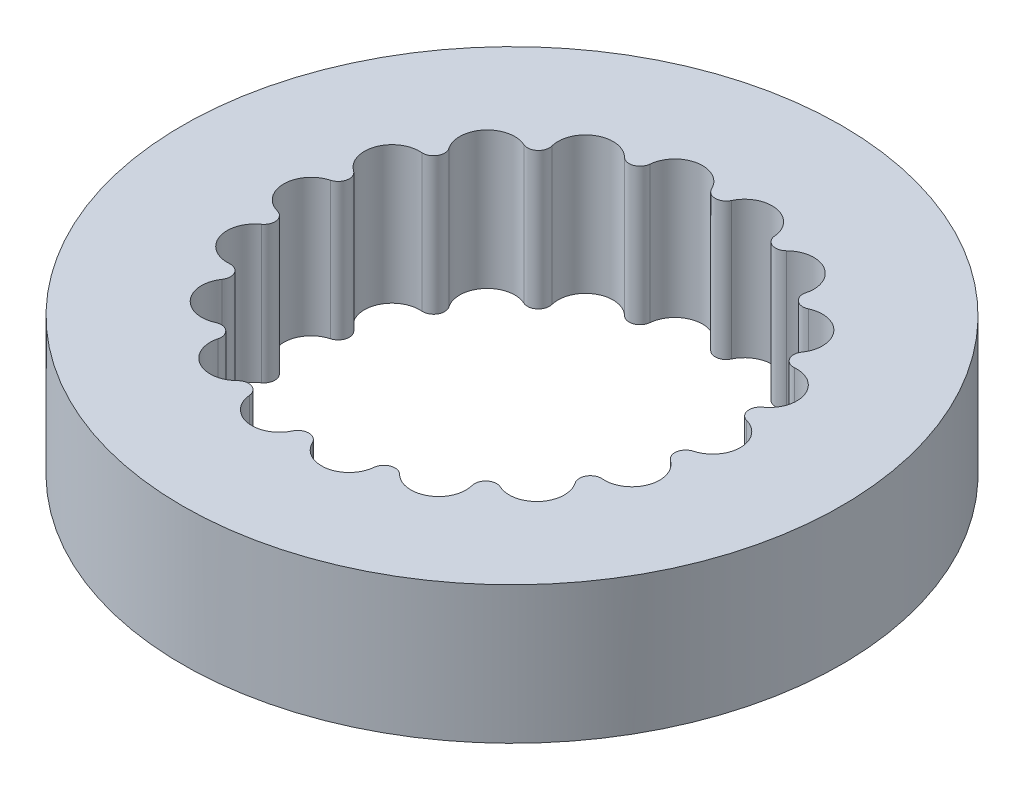
SolidWorks part; units mm, degrees
ref_plane "Front Plane" through (0, 0, 0) normal (0, 0, 1) x (1, 0, 0)
ref_plane "Top Plane" through (0, 0, 0) normal (0, 1, 0) x (1, 0, 0)
ref_plane "Right Plane" through (0, 0, 0) normal (1, 0, 0) x (0, 0, -1)
sketch "Sketch1" plane through (0, 0, 0) normal (0, 1, 0) x (1, 0, 0)
  circle A0 centre (0, 0) radius 39 construction
  circle A1 centre (0, 39) radius 2
  circle A2 centre (13.3388, 36.648) radius 2
  circle A3 centre (25.0687, 29.8757) radius 2
  circle A4 centre (33.775, 19.5) radius 2
  circle A5 centre (38.4075, 6.7723) radius 2
  circle A6 centre (38.4075, -6.7723) radius 2
  circle A7 centre (33.775, -19.5) radius 2
  circle A8 centre (25.0687, -29.8757) radius 2
  circle A9 centre (13.3388, -36.648) radius 2
  circle A10 centre (0, -39) radius 2
  circle A11 centre (-13.3388, -36.648) radius 2
  circle A12 centre (-25.0687, -29.8757) radius 2
  circle A13 centre (-33.775, -19.5) radius 2
  circle A14 centre (-38.4075, -6.7723) radius 2
  circle A15 centre (-38.4075, 6.7723) radius 2
  circle A16 centre (-33.775, 19.5) radius 2
  circle A17 centre (-25.0687, 29.8757) radius 2
  circle A18 centre (-13.3388, 36.648) radius 2
  circle A19 centre (0, 0) radius 45
  circle A20 centre (0, 0) radius 30
  point P42 (0, 0)
  dimension "D1" = 78
  dimension "D2" = 4
  dimension "D4" = 90
  dimension "D5" = 60
  dimension "D3" = 18
extrude "Boss-Extrude1" add sketch "Sketch1" along normal blind 5
sketch "Sketch2" plane through (0, 0, 0) normal (0, -1, 0) x (1, 0, 0)
  circle A0 centre (0, 0) radius 45 construction
  circle A1 centre (0, 0) radius 45
  circle A2 centre (0, 0) radius 30 construction
  circle A3 centre (0, 0) radius 30
  dimension "D1" = 90
extrude "Boss-Extrude2" add sketch "Sketch2" along normal blind 5
sketch "Sketch3" plane through (0, 0, 0) normal (0, 1, 0) x (1, 0, 0)
  circle A0 centre (-33.775, 19.5) radius 2 construction
  circle A1 centre (-38.4075, 6.7723) radius 2 construction
  circle A2 centre (-38.4075, -6.7723) radius 2 construction
  circle A3 centre (-33.775, -19.5) radius 2 construction
  circle A4 centre (-25.0687, -29.8757) radius 2 construction
  circle A5 centre (-13.3388, -36.648) radius 2 construction
  circle A6 centre (0, -39) radius 2 construction
  circle A7 centre (13.3388, -36.648) radius 2 construction
  circle A8 centre (25.0687, -29.8757) radius 2 construction
  circle A9 centre (33.775, -19.5) radius 2 construction
  circle A10 centre (38.4075, -6.7723) radius 2 construction
  circle A11 centre (38.4075, 6.7723) radius 2 construction
  circle A12 centre (33.775, 19.5) radius 2 construction
  circle A13 centre (25.0687, 29.8757) radius 2 construction
  circle A14 centre (13.3388, 36.648) radius 2 construction
  circle A15 centre (0, 39) radius 2 construction
  circle A16 centre (-13.3388, 36.648) radius 2 construction
  circle A17 centre (-25.0687, 29.8757) radius 2 construction
  arc A18 (-33.939, 17.5067) -> (-32.1308, 20.6387) centre (-33.775, 19.5) ccw
  arc A19 (-37.8799, 4.8431) -> (-37.2519, 8.4046) centre (-38.4075, 6.7723) ccw
  arc A20 (-37.2519, -8.4046) -> (-37.8799, -4.8431) centre (-38.4075, -6.7723) ccw
  arc A21 (-32.1308, -20.6387) -> (-33.939, -17.5067) centre (-33.775, -19.5) ccw
  arc A22 (-23.1342, -30.3834) -> (-25.9046, -28.0588) centre (-25.0687, -29.8757) ccw
  arc A23 (-11.3473, -36.4634) -> (-14.7457, -35.2265) centre (-13.3388, -36.648) ccw
  arc A24 (1.8082, -38.1454) -> (-1.8082, -38.1454) centre (0, -39) ccw
  arc A25 (14.7457, -35.2265) -> (11.3473, -36.4634) centre (13.3388, -36.648) ccw
  arc A26 (25.9046, -28.0588) -> (23.1342, -30.3834) centre (25.0687, -29.8757) ccw
  arc A27 (33.939, -17.5067) -> (32.1308, -20.6387) centre (33.775, -19.5) ccw
  arc A28 (37.8799, -4.8431) -> (37.2519, -8.4046) centre (38.4075, -6.7723) ccw
  arc A29 (37.2519, 8.4046) -> (37.8799, 4.8431) centre (38.4075, 6.7723) ccw
  arc A30 (32.1308, 20.6387) -> (33.939, 17.5067) centre (33.775, 19.5) ccw
  arc A31 (23.1342, 30.3834) -> (25.9046, 28.0588) centre (25.0687, 29.8757) ccw
  arc A32 (11.3473, 36.4634) -> (14.7457, 35.2265) centre (13.3388, 36.648) ccw
  arc A33 (-1.8082, 38.1454) -> (1.8082, 38.1454) centre (0, 39) ccw
  arc A34 (-14.7457, 35.2265) -> (-11.3473, 36.4634) centre (-13.3388, 36.648) ccw
  arc A35 (-25.9046, 28.0588) -> (-23.1342, 30.3834) centre (-25.0687, 29.8757) ccw
  arc A36 (-11.3473, 36.4634) -> (-1.8082, 38.1454) centre (-6.3478, 36) cw
  arc A37 (1.8082, 38.1454) -> (11.3473, 36.4634) centre (6.3478, 36) cw
  arc A38 (14.7457, 35.2265) -> (23.1342, 30.3834) centre (18.2777, 31.6579) cw
  arc A39 (25.9046, 28.0588) -> (32.1308, 20.6387) centre (28.003, 23.4973) cw
  arc A40 (33.939, 17.5067) -> (37.2519, 8.4046) centre (34.3508, 12.5027) cw
  arc A41 (37.8799, 4.8431) -> (37.8799, -4.8431) centre (36.5554, 0) cw
  arc A42 (37.2519, -8.4046) -> (33.939, -17.5067) centre (34.3508, -12.5027) cw
  arc A43 (32.1308, -20.6387) -> (25.9046, -28.0588) centre (28.003, -23.4973) cw
  arc A44 (23.1342, -30.3834) -> (14.7457, -35.2265) centre (18.2777, -31.6579) cw
  arc A45 (11.3473, -36.4634) -> (1.8082, -38.1454) centre (6.3478, -36) cw
  arc A46 (-1.8082, -38.1454) -> (-11.3473, -36.4634) centre (-6.3478, -36) cw
  arc A47 (-14.7457, -35.2265) -> (-23.1342, -30.3834) centre (-18.2777, -31.6579) cw
  arc A48 (-25.9046, -28.0588) -> (-32.1308, -20.6387) centre (-28.003, -23.4973) cw
  arc A49 (-33.939, -17.5067) -> (-37.2519, -8.4046) centre (-34.3508, -12.5027) cw
  arc A50 (-37.8799, -4.8431) -> (-37.8799, 4.8431) centre (-36.5554, 0) cw
  arc A51 (-37.2519, 8.4046) -> (-33.939, 17.5067) centre (-34.3508, 12.5027) cw
  arc A52 (-32.1308, 20.6387) -> (-25.9046, 28.0588) centre (-28.003, 23.4973) cw
  arc A53 (-23.1342, 30.3834) -> (-14.7457, 35.2265) centre (-18.2777, 31.6579) cw
  circle A56 centre (0, 0) radius 60
  point P111 (0, 0)
  dimension "D3" = 120
  dimension "D1" = 3
  dimension "D2" = 18
extrude "Boss-Extrude3" add sketch "Sketch3" along normal blind 20
sketch "Sketch4" plane through (0, 5, 0) normal (0, 1, 0) x (1, 0, 0)
  arc A36 (-1.8082, 38.1454) -> (-11.3473, 36.4634) centre (-6.3478, 36) ccw
  arc A37 (-14.7457, 35.2265) -> (-11.3473, 36.4634) centre (-13.3388, 36.648) ccw
  arc A38 (-14.7457, 35.2265) -> (-23.1342, 30.3834) centre (-18.2777, 31.6579) ccw
  arc A39 (-25.9046, 28.0588) -> (-23.1342, 30.3834) centre (-25.0687, 29.8757) ccw
  arc A40 (-25.9046, 28.0588) -> (-32.1308, 20.6387) centre (-28.003, 23.4973) ccw
  arc A41 (-33.939, 17.5067) -> (-32.1308, 20.6387) centre (-33.775, 19.5) ccw
  arc A42 (-33.939, 17.5067) -> (-37.2519, 8.4046) centre (-34.3508, 12.5027) ccw
  arc A43 (-37.8799, 4.8431) -> (-37.2519, 8.4046) centre (-38.4075, 6.7723) ccw
  arc A44 (-37.8799, 4.8431) -> (-37.8799, -4.8431) centre (-36.5554, 0) ccw
  arc A45 (-37.2519, -8.4046) -> (-37.8799, -4.8431) centre (-38.4075, -6.7723) ccw
  arc A46 (-37.2519, -8.4046) -> (-33.939, -17.5067) centre (-34.3508, -12.5027) ccw
  arc A47 (-32.1308, -20.6387) -> (-33.939, -17.5067) centre (-33.775, -19.5) ccw
  arc A48 (-32.1308, -20.6387) -> (-25.9046, -28.0588) centre (-28.003, -23.4973) ccw
  arc A49 (-23.1342, -30.3834) -> (-25.9046, -28.0588) centre (-25.0687, -29.8757) ccw
  arc A50 (-23.1342, -30.3834) -> (-14.7457, -35.2265) centre (-18.2777, -31.6579) ccw
  arc A51 (-11.3473, -36.4634) -> (-14.7457, -35.2265) centre (-13.3388, -36.648) ccw
  arc A52 (-11.3473, -36.4634) -> (-1.8082, -38.1454) centre (-6.3478, -36) ccw
  arc A53 (1.8082, -38.1454) -> (-1.8082, -38.1454) centre (0, -39) ccw
  arc A54 (1.8082, -38.1454) -> (11.3473, -36.4634) centre (6.3478, -36) ccw
  arc A55 (14.7457, -35.2265) -> (11.3473, -36.4634) centre (13.3388, -36.648) ccw
  arc A56 (14.7457, -35.2265) -> (23.1342, -30.3834) centre (18.2777, -31.6579) ccw
  arc A57 (25.9046, -28.0588) -> (23.1342, -30.3834) centre (25.0687, -29.8757) ccw
  arc A58 (25.9046, -28.0588) -> (32.1308, -20.6387) centre (28.003, -23.4973) ccw
  arc A59 (33.939, -17.5067) -> (32.1308, -20.6387) centre (33.775, -19.5) ccw
  arc A60 (33.939, -17.5067) -> (37.2519, -8.4046) centre (34.3508, -12.5027) ccw
  arc A61 (37.8799, -4.8431) -> (37.2519, -8.4046) centre (38.4075, -6.7723) ccw
  arc A62 (37.8799, -4.8431) -> (37.8799, 4.8431) centre (36.5554, 0) ccw
  arc A63 (37.2519, 8.4046) -> (37.8799, 4.8431) centre (38.4075, 6.7723) ccw
  arc A64 (37.2519, 8.4046) -> (33.939, 17.5067) centre (34.3508, 12.5027) ccw
  arc A65 (32.1308, 20.6387) -> (33.939, 17.5067) centre (33.775, 19.5) ccw
  arc A66 (32.1308, 20.6387) -> (25.9046, 28.0588) centre (28.003, 23.4973) ccw
  arc A67 (23.1342, 30.3834) -> (25.9046, 28.0588) centre (25.0687, 29.8757) ccw
  arc A68 (23.1342, 30.3834) -> (14.7457, 35.2265) centre (18.2777, 31.6579) ccw
  arc A69 (11.3473, 36.4634) -> (14.7457, 35.2265) centre (13.3388, 36.648) ccw
  arc A70 (11.3473, 36.4634) -> (1.8082, 38.1454) centre (6.3478, 36) ccw
  arc A71 (-1.8082, 38.1454) -> (1.8082, 38.1454) centre (0, 39) ccw
  arc A72 (-1.8082, 38.1454) -> (-11.3473, 36.4634) centre (-6.3478, 36) ccw
  arc A73 (-14.7457, 35.2265) -> (-11.3473, 36.4634) centre (-13.3388, 36.648) ccw
  arc A74 (-14.7457, 35.2265) -> (-23.1342, 30.3834) centre (-18.2777, 31.6579) ccw
  arc A75 (-25.9046, 28.0588) -> (-23.1342, 30.3834) centre (-25.0687, 29.8757) ccw
  arc A76 (-25.9046, 28.0588) -> (-32.1308, 20.6387) centre (-28.003, 23.4973) ccw
  arc A77 (-33.939, 17.5067) -> (-32.1308, 20.6387) centre (-33.775, 19.5) ccw
  arc A78 (-33.939, 17.5067) -> (-37.2519, 8.4046) centre (-34.3508, 12.5027) ccw
  arc A79 (-37.8799, 4.8431) -> (-37.2519, 8.4046) centre (-38.4075, 6.7723) ccw
  arc A80 (-37.8799, 4.8431) -> (-37.8799, -4.8431) centre (-36.5554, 0) ccw
  arc A81 (-37.2519, -8.4046) -> (-37.8799, -4.8431) centre (-38.4075, -6.7723) ccw
  arc A82 (-37.2519, -8.4046) -> (-33.939, -17.5067) centre (-34.3508, -12.5027) ccw
  arc A83 (-32.1308, -20.6387) -> (-33.939, -17.5067) centre (-33.775, -19.5) ccw
  arc A84 (-32.1308, -20.6387) -> (-25.9046, -28.0588) centre (-28.003, -23.4973) ccw
  arc A85 (-23.1342, -30.3834) -> (-25.9046, -28.0588) centre (-25.0687, -29.8757) ccw
  arc A86 (-23.1342, -30.3834) -> (-14.7457, -35.2265) centre (-18.2777, -31.6579) ccw
  arc A87 (-11.3473, -36.4634) -> (-14.7457, -35.2265) centre (-13.3388, -36.648) ccw
  arc A88 (-11.3473, -36.4634) -> (-1.8082, -38.1454) centre (-6.3478, -36) ccw
  arc A89 (1.8082, -38.1454) -> (-1.8082, -38.1454) centre (0, -39) ccw
  arc A90 (1.8082, -38.1454) -> (11.3473, -36.4634) centre (6.3478, -36) ccw
  arc A91 (14.7457, -35.2265) -> (11.3473, -36.4634) centre (13.3388, -36.648) ccw
  arc A92 (14.7457, -35.2265) -> (23.1342, -30.3834) centre (18.2777, -31.6579) ccw
  arc A93 (25.9046, -28.0588) -> (23.1342, -30.3834) centre (25.0687, -29.8757) ccw
  arc A94 (25.9046, -28.0588) -> (32.1308, -20.6387) centre (28.003, -23.4973) ccw
  arc A95 (33.939, -17.5067) -> (32.1308, -20.6387) centre (33.775, -19.5) ccw
  arc A96 (33.939, -17.5067) -> (37.2519, -8.4046) centre (34.3508, -12.5027) ccw
  arc A97 (37.8799, -4.8431) -> (37.2519, -8.4046) centre (38.4075, -6.7723) ccw
  arc A98 (37.8799, -4.8431) -> (37.8799, 4.8431) centre (36.5554, 0) ccw
  arc A99 (37.2519, 8.4046) -> (37.8799, 4.8431) centre (38.4075, 6.7723) ccw
  arc A100 (37.2519, 8.4046) -> (33.939, 17.5067) centre (34.3508, 12.5027) ccw
  arc A101 (32.1308, 20.6387) -> (33.939, 17.5067) centre (33.775, 19.5) ccw
  arc A102 (32.1308, 20.6387) -> (25.9046, 28.0588) centre (28.003, 23.4973) ccw
  arc A103 (23.1342, 30.3834) -> (25.9046, 28.0588) centre (25.0687, 29.8757) ccw
  arc A104 (23.1342, 30.3834) -> (14.7457, 35.2265) centre (18.2777, 31.6579) ccw
  arc A105 (11.3473, 36.4634) -> (14.7457, 35.2265) centre (13.3388, 36.648) ccw
  arc A106 (11.3473, 36.4634) -> (1.8082, 38.1454) centre (6.3478, 36) ccw
  arc A107 (-1.8082, 38.1454) -> (1.8082, 38.1454) centre (0, 39) ccw
  dimension "D1" = 0
extrude "Cut-Extrude1" cut sketch "Sketch4" against normal up to next
sketch "Sketch5" plane through (0, 0, 0) normal (0, -1, 0) x (1, 0, 0)
  circle A1 centre (0, 0) radius 45 construction
  circle A3 centre (0, 0) radius 60 construction
  circle A4 centre (0, 0) radius 45
  circle A5 centre (0, 0) radius 60
extrude "Boss-Extrude4" add sketch "Sketch5" along normal blind 5
